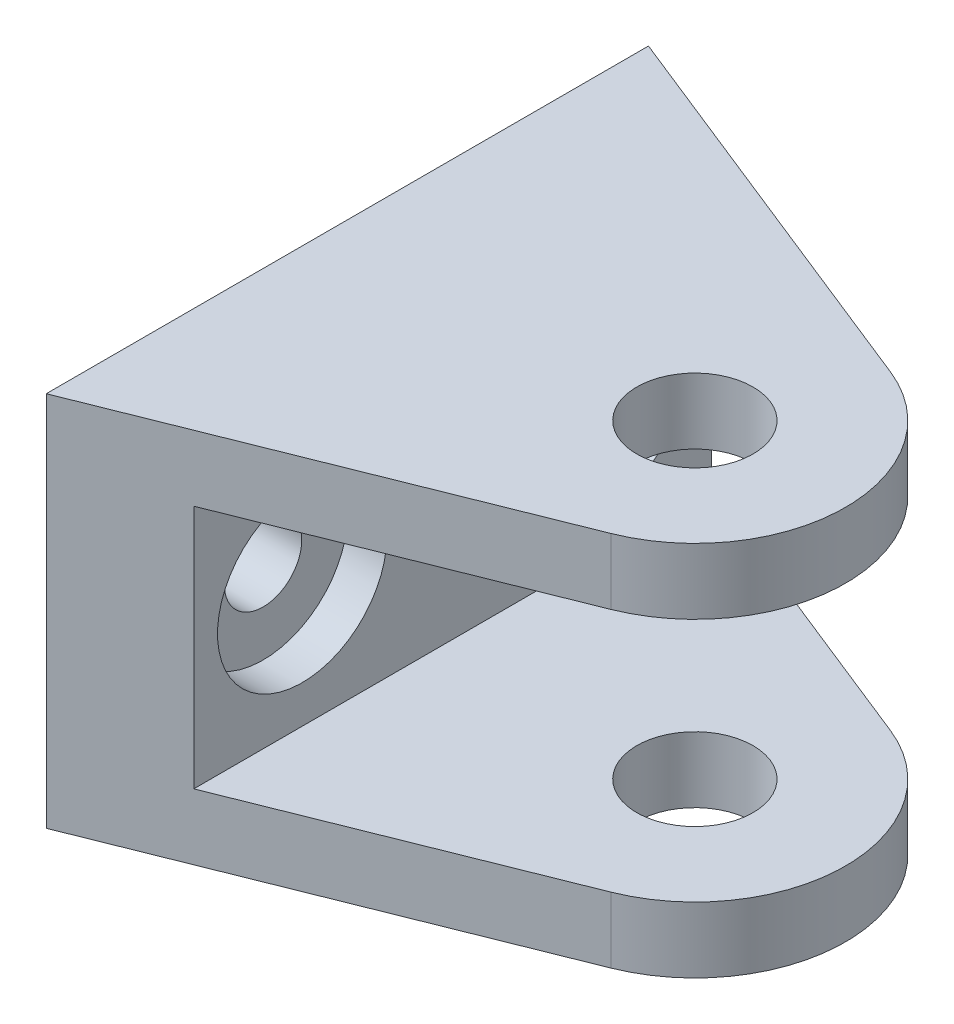
SolidWorks part; units mm, degrees
material "6061-T6 (SS)"
ref_plane "Front Plane" through (0, 0, 0) normal (0, 0, 1) x (1, 0, 0)
ref_plane "Top Plane" through (0, 0, 0) normal (0, 1, 0) x (1, 0, 0)
ref_plane "Right Plane" through (0, 0, 0) normal (1, 0, 0) x (0, 0, -1)
sketch "Sketch1" plane through (0, 0, 0) normal (0, 0, 1) x (1, 0, 0)
  line L0 (0, 0) -> (42.0157, 0)
  line L1 (42.0157, 0) -> (42.0157, 5.5499)
  line L2 (42.0157, 5.5499) -> (8.89, 5.5499)
  line L3 (8.89, 5.5499) -> (8.89, 26.2001)
  line L4 (8.89, 26.2001) -> (42.0157, 26.2001)
  line L5 (42.0157, 26.2001) -> (42.0157, 31.75)
  line L6 (42.0157, 31.75) -> (0, 31.75)
  line L7 (0, 31.75) -> (0, 0)
  line L8 (29.3157, 31.75) -> (29.3157, 0) construction
  dimension "D1" = 31.75
  dimension "D2" = 20.6502
  dimension "D3" = 12.7
  dimension "D4" = 8.89
extrude "Boss-Extrude1" add sketch "Sketch1" along normal blind 50.8
sketch "Sketch2" plane through (8.89, 0, 0) normal (1, 0, 0) x (0, 0, -1)
  line L0 (-25.4, 31.75) -> (-25.4, 0) construction
  line L1 (-50.8, 31.75) -> (0, 31.75) construction
  line L2 (-50.8, 0) -> (0, 0) construction
  line L3 (-38.1, 15.875) -> (-12.7, 15.875) construction
  circle A0 centre (-38.1, 15.875) radius 3.175
  circle A1 centre (-12.7, 15.875) radius 3.175
  point P6 (-38.1, 15.875)
  point P7 (-12.7, 15.875)
  point P8 (-25.4, 15.875)
  point P15 (-12.7, 15.875)
  point P17 (-38.1, 15.875)
  dimension "D2" = 6.35
  dimension "D1" = 25.4
hole_wizard "CBORE for 1/4 Binding Head Machine Screw1" positions "Sketch2" profile "Sketch7" counterbore size "1/4" standard "ANSI Inch" end condition through all
sketch "Sketch7" plane through (8.89, 15.875, 38.1) normal (0, 1, 0) x (0, 0, -1)
  line L0 (0, 0) -> (0, 8.89)
  line L1 (0, 8.89) -> (3.2639, 8.89)
  line L3 (3.2639, 8.89) -> (3.2639, 3.302)
  line L4 (3.2639, 3.302) -> (7.1437, 3.302)
  line L5 (7.1437, 3.302) -> (7.1437, 0)
  line L7 (7.1437, 0) -> (0, 0)
  line L11 (0, -6.35) -> (0, 107.95) construction
  dimension "Thru Hole Dia." = 6.5278
  dimension "Thru Hole Depth" = 8.89
  dimension "C'Bore Dia." = 14.2875
  dimension "C'Bore Depth" = 3.302
sketch "Sketch3" plane through (0, 0, 0) normal (0, -1, 0) x (1, 0, 0)
  line L0 (34701.1242, 25.4) -> (-34766.6696, 25.4) construction
  circle A0 centre (29.3157, 25.4) radius 4.9022
  dimension "D1" = 9.8044
extrude "3/8 Close Fit Hole" cut sketch "Sketch3" against normal up to surface (31.75 mm away) up to face at (21.0078, 31.75, 25.4)
sketch "Sketch4" plane through (0, 31.75, 0) normal (0, 1, 0) x (1, 0, 0)
  line L0 (42.0157, -50.8) -> (42.0157, 0) construction
  line L1 (0, 0) -> (34.031, -13.6078)
  line L2 (0, -50.8) -> (34.031, -37.1922)
  line L5 (0, 0) -> (0, -50.8)
  arc A0 (34.031, -37.1922) -> (34.031, -13.6078) centre (29.3157, -25.4) ccw
extrude "Rounding" cut sketch "Sketch4" against normal up to surface (31.75 mm away) flip side to cut up to face at (29.3157, 0, 20.4978)
